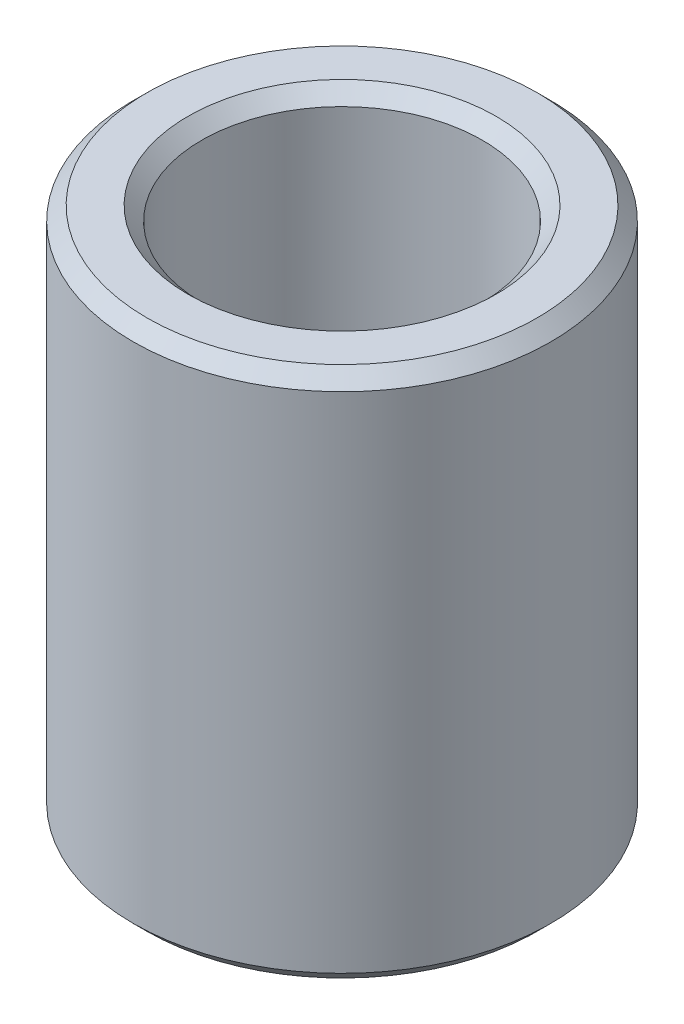
SolidWorks part; units mm, degrees
ref_plane "Front Plane" through (0, 0, 0) normal (0, 0, 1) x (1, 0, 0)
ref_plane "Top Plane" through (0, 0, 0) normal (0, 1, 0) x (1, 0, 0)
ref_plane "Right Plane" through (0, 0, 0) normal (1, 0, 0) x (0, 0, -1)
sketch "Sketch1" plane through (0, 0, 0) normal (0, 1, 0) x (1, 0, 0)
  circle A0 centre (0, 0) radius 10
  dimension "SLEEVE_OD" = 20
extrude "Boss-Extrude1" add sketch "Sketch1" along normal blind 25.4324
sketch "Sketch2" plane through (0, 0, 0) normal (0, 1, 0) x (1, 0, 0)
  circle A0 centre (0, 0) radius 6.7191
  dimension "BORE_D" = 13.4382
extrude "Cut-Extrude1" cut sketch "Sketch2" along normal through all
chamfer "Chamfer1" distance 0.6595 angle 45 4 edges at (0, 25.4324, 6.7191) (0, 0, 6.7191) (0, 0, 10) (0, 25.4324, 10)
